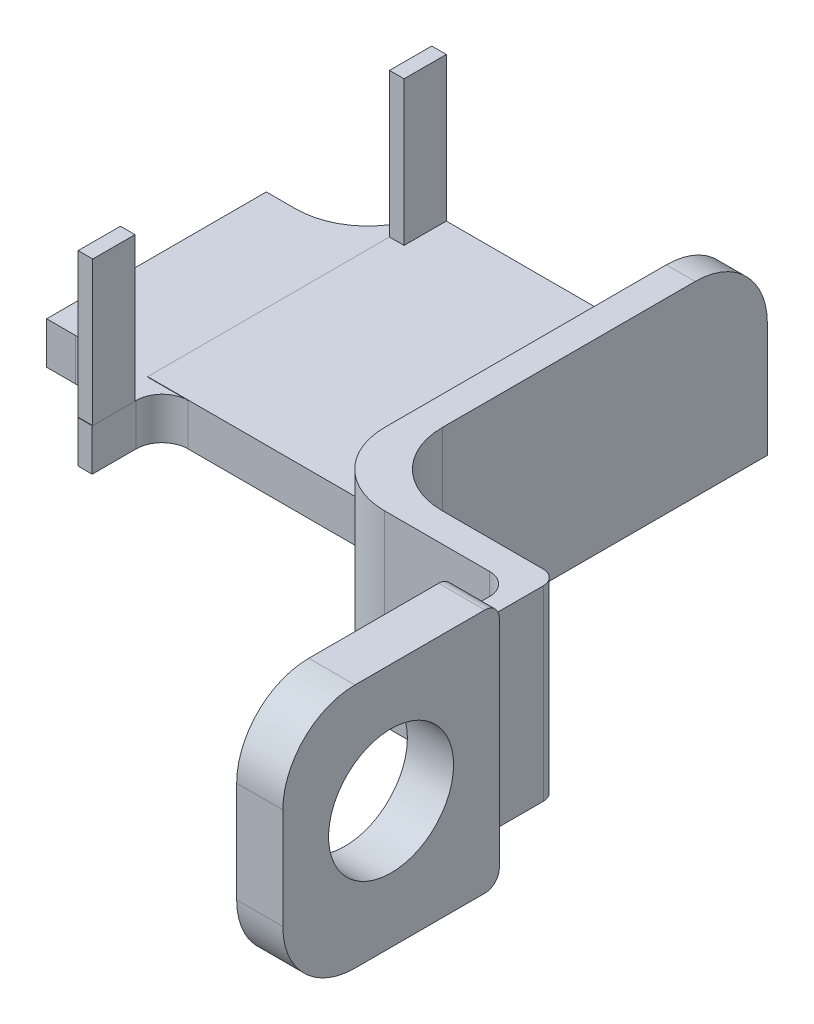
SolidWorks part; units mm, degrees
ref_plane "Front Plane" through (0, 0, 0) normal (0, 0, 1) x (1, 0, 0)
ref_plane "Top Plane" through (0, 0, 0) normal (0, 1, 0) x (1, 0, 0)
ref_plane "Right Plane" through (0, 0, 0) normal (1, 0, 0) x (0, 0, -1)
sketch "Sketch1" plane through (0, 0, 0) normal (0, 1, 0) x (1, 0, 0)
  line L1 (-16.9261, 31.7121) -> (37.0739, 31.7121)
  line L2 (-16.9261, 31.7121) -> (-16.9261, -18.2879)
  line L3 (-16.9261, -18.2879) -> (37.0739, -18.2879)
  line L4 (37.0739, 31.7121) -> (37.0739, -18.2879)
  dimension "D1" = 50
  dimension "D2" = 54
extrude "Boss-Extrude1" add sketch "Sketch1" along normal blind 7.46 contours L1 L4 L3 L2
sketch "Sketch2" plane through (37.0739, 0, 0) normal (1, 0, 0) x (0, 0, -1)
  line L1 (31.7121, 7.46) -> (-43.2879, 7.46)
  line L2 (31.7121, 7.46) -> (31.7121, 0)
  line L3 (31.7121, 0) -> (-43.2879, 0)
  line L4 (-43.2879, 7.46) -> (-43.2879, 0)
  dimension "D1" = 75
extrude "Boss-Extrude2" add sketch "Sketch2" along normal blind 5.08
sketch "Sketch4" plane through (0, 7.46, 0) normal (0, 1, 0) x (1, 0, 0)
  line L1 (42.1539, 31.7121) -> (37.0739, 31.7121)
  line L2 (42.1539, 31.7121) -> (42.1539, -43.2879)
  line L3 (42.1539, -43.2879) -> (37.0739, -43.2879)
  line L4 (37.0739, 31.7121) -> (37.0739, -43.2879)
extrude "Boss-Extrude3" add sketch "Sketch4" along normal blind 25.4 contours L4 L3 L2 L1
fillet "Fillet1" radius 12.7 1 edges at (39.6139, 32.86, -31.7121)
sketch "Sketch6" plane through (42.1539, 0, 0) normal (1, 0, 0) x (0, 0, -1)
  line L0 (-43.2879, 0) -> (31.7121, 0) construction
  line L1 (-43.2879, 32.86) -> (-38.2079, 32.86)
  line L2 (-43.2879, 32.86) -> (-43.2879, 0)
  line L3 (-43.2879, 0) -> (-38.2079, 0)
  line L4 (-38.2079, 32.86) -> (-38.2079, 0)
  dimension "D1" = 5.08
extrude "Boss-Extrude4" add sketch "Sketch6" along normal blind 33.02 contours L2 L3 L4 L1
fillet "Fillet2" radius 12.7 1 edges at (42.1539, 16.43, 38.2079)
fillet "Fillet3" radius 12.7 1 edges at (37.0739, 16.43, 43.2879)
sketch "Sketch9" plane through (0, 0, 43.2879) normal (0, 0, 1) x (1, 0, 0)
  line L0 (75.1739, 0) -> (49.7739, 0) construction
  line L1 (75.1739, 32.86) -> (72.0848, 32.86)
  line L2 (75.1739, 32.86) -> (75.1739, 0)
  line L3 (75.1739, 0) -> (72.0848, 0)
  line L4 (72.0848, 32.86) -> (72.0848, 0)
extrude "Boss-Extrude5" add sketch "Sketch9" along normal blind 10
sketch "Sketch10" plane through (0, 0, 53.2879) normal (0, 0, 1) x (1, 0, 0)
  line L5 (79.9689, -4.0631) -> (71.8409, -4.0631)
  line L6 (79.9689, -4.0631) -> (79.9689, 39.1169)
  line L7 (79.9689, 39.1169) -> (71.8409, 39.1169)
  line L8 (71.8409, -4.0631) -> (71.8409, 39.1169)
  dimension "D1" = 43.18
  dimension "D2" = 8.128
extrude "Boss-Extrude6" add sketch "Sketch10" along normal blind 38.1
sketch "Sketch11" plane through (79.9689, 0, 0) normal (1, 0, 0) x (0, 0, -1)
  line L0 (-91.3879, -4.0631) -> (-91.3879, 39.1169) construction
  circle A0 centre (-72.3379, 18.2756) radius 11
  dimension "D1" = 19.05
fillet "Fillet4" radius 12.7 2 edges at (75.9049, -4.0631, 91.3879) (75.9049, 39.1169, 91.3879)
fillet "Fillet5" radius 2.54 2 edges at (75.9049, -4.0631, 53.2879) (75.9049, 39.1169, 53.2879)
extrude "Cut-Extrude1" cut sketch "Sketch11" against normal blind 38.1 contours A0
fillet "Fillet6" radius 2.54 1 edges at (75.1739, 16.43, 38.2079)
fillet "Fillet7" radius 3.81 1 edges at (72.0848, 16.43, 43.2879)
sketch "Sketch18" plane through (-16.9261, 0, 0) normal (-1, 0, 0) x (0, 0, 1)
  line L0 (-31.7121, 0) -> (18.2879, 0) construction
  line L1 (-20.383, 0) -> (30.5879, 0)
  line L2 (-20.383, 0) -> (-20.383, 7.391)
  line L3 (-20.383, 7.391) -> (30.5879, 7.391)
  line L4 (30.5879, 0) -> (30.5879, 7.391)
  line L5 (30.5879, 0) -> (30.5879, 32.86) construction
extrude "Boss-Extrude8" add sketch "Sketch18" along normal blind 17.78
fillet "Fillet12" radius 12.7 1 edges at (-16.9261, 3.6955, -20.383)
sketch "Sketch23" plane through (-16.9261, 0, 0) normal (1, 0, 0) x (0, 0, -1)
  line L1 (-30.5879, 7.391) -> (-18.2879, 7.391)
  line L2 (-30.5879, 7.391) -> (-30.5879, 0)
  line L3 (-30.5879, 0) -> (-18.2879, 0)
  line L4 (-18.2879, 7.391) -> (-18.2879, 0)
extrude "Boss-Extrude9" add sketch "Sketch23" along normal blind 7.62
sketch "Sketch24" plane through (0, 7.46, 0) normal (0, 1, 0) x (1, 0, 0)
  line L0 (-16.9261, 31.7121) -> (-16.9261, -18.2879) construction
  line L1 (-16.9261, 31.7121) -> (-14.3565, 31.7121)
  line L2 (-16.9261, 31.7121) -> (-16.9261, 24.2766)
  line L3 (-16.9261, 24.2766) -> (-14.3565, 24.2766)
  line L4 (-14.3565, 31.7121) -> (-14.3565, 24.2766)
  line L5 (-16.856, -23.1556) -> (-14.2864, -23.1556)
  line L6 (-16.856, -23.1556) -> (-16.856, -30.5911)
  line L7 (-16.856, -30.5911) -> (-14.2864, -30.5911)
  line L8 (-14.2864, -23.1556) -> (-14.2864, -30.5911)
extrude "Boss-Extrude10" add sketch "Sketch24" along normal blind 25.4
sketch "Sketch28" plane through (0, 7.391, 0) normal (0, 1, 0) x (1, 0, 0)
  line L1 (-34.7061, -30.5879) -> (-16.9261, -30.5879)
  line L2 (-34.7061, -30.5879) -> (-34.7061, -18.2879)
  line L3 (-34.7061, -18.2879) -> (-16.9261, -18.2879)
  line L4 (-16.9261, -30.5879) -> (-16.9261, -18.2879)
extrude "Cut-Extrude8" cut sketch "Sketch28" against normal blind 25.4 contours L1 L4 L3 L2
fillet "Fillet14" radius 12.7 1 edges at (-16.9261, 3.6955, 18.2879)
sketch "Sketch30" plane through (-9.3061, 0, 0) normal (1, 0, 0) x (0, 0, -1)
  line L1 (-18.2879, 7.391) -> (-30.5879, 7.391)
  line L2 (-18.2879, 7.391) -> (-18.2879, 0)
  line L3 (-18.2879, 0) -> (-30.5879, 0)
  line L4 (-30.5879, 7.391) -> (-30.5879, 0)
extrude "Cut-Extrude9" cut sketch "Sketch30" against normal blind 5.08
fillet "Fillet16" radius 4.572 1 edges at (-14.3861, 3.6955, 18.2879)
